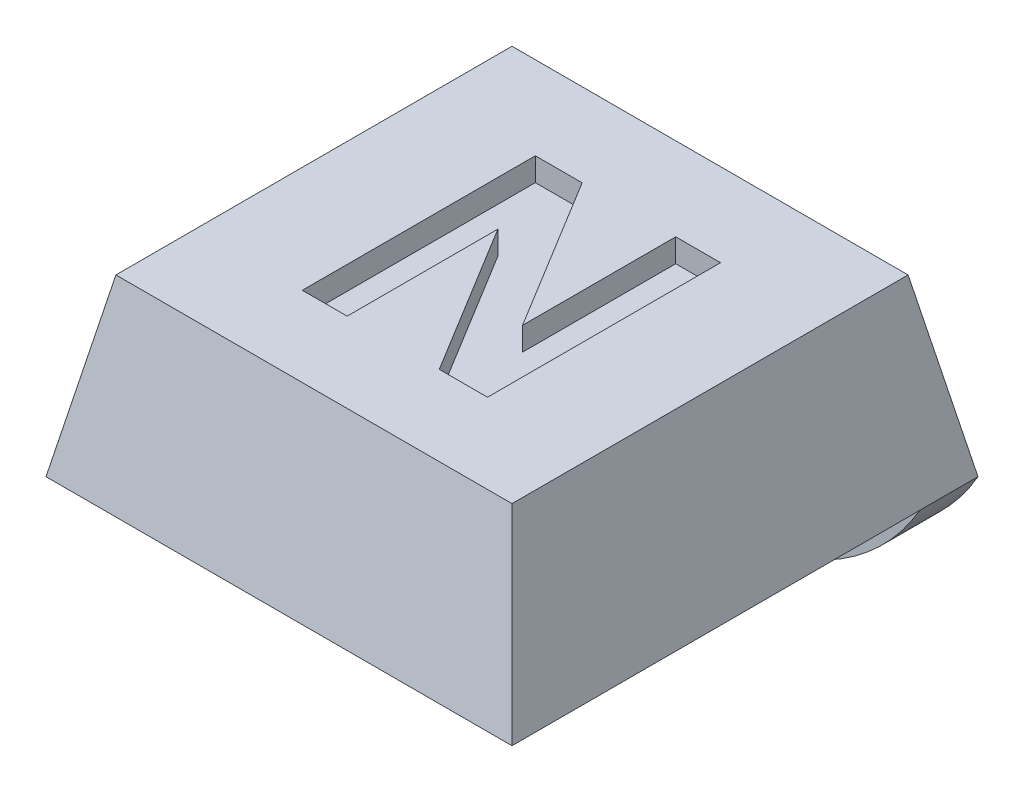
SolidWorks part; units mm, degrees
ref_plane "Front Plane" through (0, 0, 0) normal (0, 0, 1) x (1, 0, 0)
ref_plane "Top Plane" through (0, 0, 0) normal (0, 1, 0) x (1, 0, 0)
ref_plane "Right Plane" through (0, 0, 0) normal (1, 0, 0) x (0, 0, -1)
sketch "Sketch1" plane through (0, 0, 0) normal (0, 1, 0) x (1, 0, 0)
  line L1 (0, 0) -> (8, 0)
  line L2 (0, 0) -> (0, 8)
  line L3 (0, 8) -> (8, 8)
  line L4 (8, 0) -> (8, 8)
  dimension "D1" = 8
  dimension "D2" = 8
extrude "Boss-Extrude1" add sketch "Sketch1" along normal blind 3
sketch "Sketch2" plane through (0, 0, 0) normal (0, 0, 1) x (1, 0, 0)
  line L0 (0, 0) -> (0.6, 3)
  line L1 (0, 3) -> (8, 3) construction
  line L2 (0.6, 3) -> (0, 3)
  line L3 (0, 3) -> (0, 0)
  line L4 (8, 0) -> (7.4, 3)
  line L5 (7.4, 3) -> (8, 3)
  line L6 (8, 3) -> (8, 0)
  dimension "D1" = 0.6
  dimension "D2" = 0.6
extrude "Cut-Extrude1" cut sketch "Sketch2" against normal through all both and the other way through all
sketch "Sketch3" plane through (0, 0, 0) normal (1, 0, 0) x (0, 0, -1)
  line L0 (0, 0) -> (0.6, 3)
  line L1 (8, 3) -> (0, 3) construction
  line L2 (0.6, 3) -> (0, 3)
  line L3 (0, 3) -> (0, 0)
  line L4 (8, 3) -> (7.4, 3)
  line L5 (7.4, 3) -> (8, 0)
  line L6 (8, 3) -> (8, 0)
  dimension "D1" = 0.6
  dimension "D2" = 0.6
extrude "Cut-Extrude2" cut sketch "Sketch3" along normal blind 11
sketch "Sketch4" plane through (0, 0, 0) normal (0, -1, 0) x (1, 0, 0)
  line L0 (8, 0) -> (8, -8) construction
  line L3 (0, 0) -> (8, 0) construction
  circle A0 centre (4, -3.75) radius 1.8
  dimension "D1" = 3.6
  dimension "D2" = 4
  dimension "D3" = 3.75
extrude "Cut-Extrude3" cut sketch "Sketch4" against normal blind 0.8
sketch "Sketch5" plane through (0, 0, 0) normal (0, -1, 0) x (1, 0, 0)
  line L0 (8, 0) -> (8, -8) construction
  line L1 (0, -8) -> (8, -8)
  line L2 (0, -8) -> (0, -7)
  line L3 (0, -7) -> (8, -7)
  line L4 (8, -8) -> (8, -7)
  dimension "D1" = 1
extrude "Boss-Extrude2" add sketch "Sketch5" along normal blind 2
fillet "Fillet1" radius 4 2 edges at (8, -2, -7.5) (0, -2, -7.5)
sketch "Sketch6" plane through (0, 3, 0) normal (0, 1, 0) x (1, 0, 0)
  text T0 "N" font "Arial" height 4
extrude "Cut-Extrude4" cut sketch "Sketch6" against normal blind 0.4
